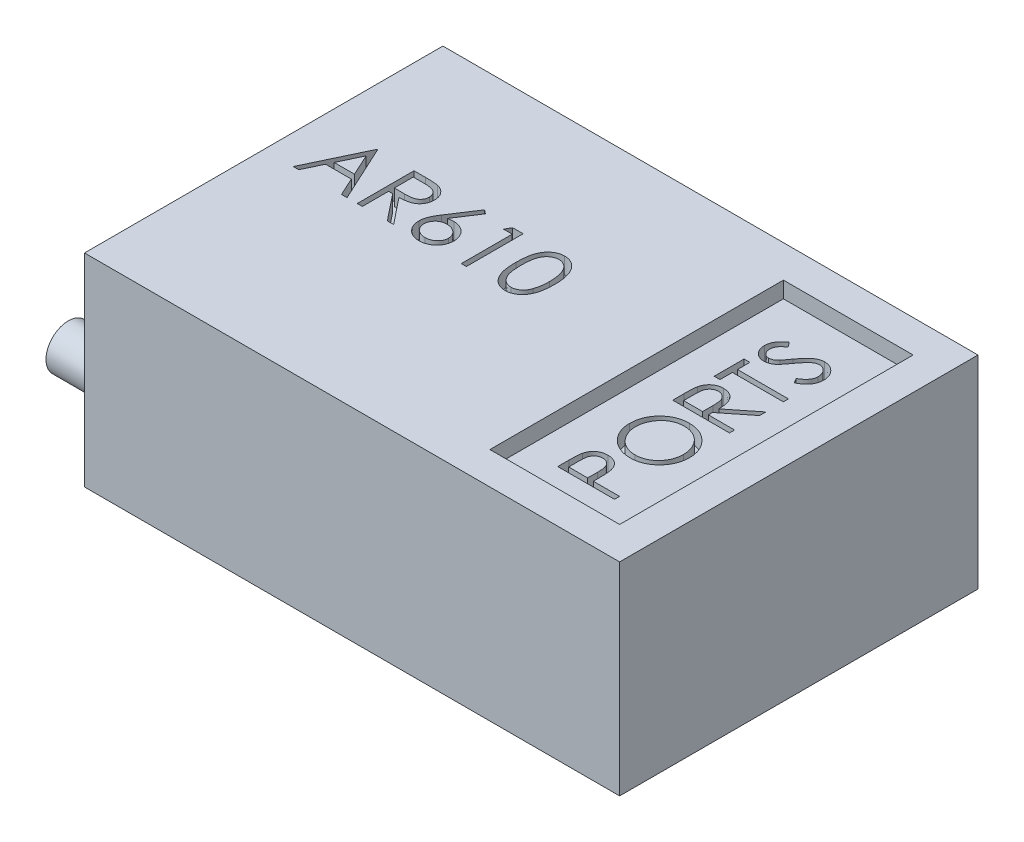
SolidWorks part; units mm, degrees
ref_plane "Front Plane" through (0, 0, 0) normal (0, 0, 1) x (1, 0, 0)
ref_plane "Top Plane" through (0, 0, 0) normal (0, 1, 0) x (1, 0, 0)
ref_plane "Right Plane" through (0, 0, 0) normal (1, 0, 0) x (0, 0, -1)
ref_axis "X" through (-88.99, 0, 0) along (1, 0, 0)
ref_axis "Y" through (0, 55, 0) along (0, -1, 0)
ref_axis "Z" through (0, 0, -88.99) along (0, 0, 1)
sketch "Sketch1" plane through (0, 0, 0) normal (0, 1, 0) x (1, 0, 0)
  line L0 (0, 0) -> (10.5, 0) construction
  line L1 (-16.5, 11.05) -> (16.5, 11.05)
  line L2 (-16.5, 11.05) -> (-16.5, -11.05)
  line L3 (-16.5, -11.05) -> (16.5, -11.05)
  line L4 (16.5, 11.05) -> (16.5, -11.05)
  line L5 (-16.5, 11.05) -> (16.5, -11.05) construction
  line L6 (-16.5, -11.05) -> (16.5, 11.05) construction
  line L7 (14.5, 9.05) -> (14.5, 11.05) construction
  line L8 (6.5, 9.05) -> (14.5, 9.05)
  line L9 (6.5, 9.05) -> (6.5, -9.05)
  line L10 (6.5, -9.05) -> (14.5, -9.05)
  line L11 (14.5, 9.05) -> (14.5, -9.05)
  line L12 (6.5, 9.05) -> (14.5, -9.05) construction
  line L13 (6.5, -9.05) -> (14.5, 9.05) construction
  line L14 (14.5, 9.05) -> (16.5, 9.05) construction
  point P0 (0, 0)
  dimension "D1" = 22.1
  dimension "D2" = 33
  dimension "D3" = 8
  dimension "D4" = 2
extrude "Boss-Extrude1" add sketch "Sketch1" along normal blind 12.5 contours L2 L3 L4 L1
extrude "Cut-Extrude1" cut sketch "Sketch1<3>" against normal blind 1 from surface contours L11 L8 L9 L10 region at (10.5, 0, 0) starting at face at (0, 12.5, 0)
sketch "Sketch1<3>" plane through (0, 0, 0) normal (0, 1, 0) x (1, 0, 0) same geometry as "Sketch1"
sketch "Sketch2" plane through (0, 11.5, 0) normal (0, 1, 0) x (1, 0, 0)
  line L0 (0, 0) -> (12, 0) construction
  line L1 (12, 8) -> (12, -8) construction
  text T0 "PORTS"
  point P3 (0, 0)
  point P6 (12, 0)
  point P7 (12.4976, -7.817)
  dimension "D1" = 12
  dimension "D2" = 16
extrude "Cut-Extrude2" cut sketch "Sketch2" against normal blind 1
sketch "Sketch3" plane through (0, 12.5, 0) normal (0, 1, 0) x (1, 0, 0)
  line L0 (0, 0) -> (-15, 0) construction
  text T0 "AR610"
  point P0 (-15, 0)
  point P4 (0, 0)
  dimension "D1" = 15
extrude "Cut-Extrude3" cut sketch "Sketch3" against normal blind 1
sketch "Sketch4" plane through (-16.5, 0, 0) normal (-1, 0, 0) x (0, 0, 1)
  line L0 (8.05, 0) -> (8.05, 4) construction
  line L1 (-11.05, 0) -> (11.05, 0) construction
  line L2 (8.05, 4) -> (11.05, 4) construction
  line L3 (11.05, 12.5) -> (11.05, 0) construction
  circle A0 centre (8.05, 4) radius 1.375
  dimension "D3" = 2.75
  dimension "D1" = 4
  dimension "D2" = 3
extrude "Boss-Extrude2" add sketch "Sketch4" along normal blind 4
sketch "Sketch5" plane through (0, 0, -11.05) normal (0, 0, -1) x (-1, 0, 0)
  line L0 (13.5, 0) -> (13.5, 4) construction
  line L1 (16.5, 0) -> (-16.5, 0) construction
  line L2 (13.5, 4) -> (16.5, 4) construction
  line L4 (16.5, 12.5) -> (16.5, 0) construction
  circle A0 centre (13.5, 4) radius 1.375
  dimension "D3" = 2.75
  dimension "D1" = 4
  dimension "D2" = 3
extrude "Boss-Extrude3" add sketch "Sketch5" along normal blind 4
